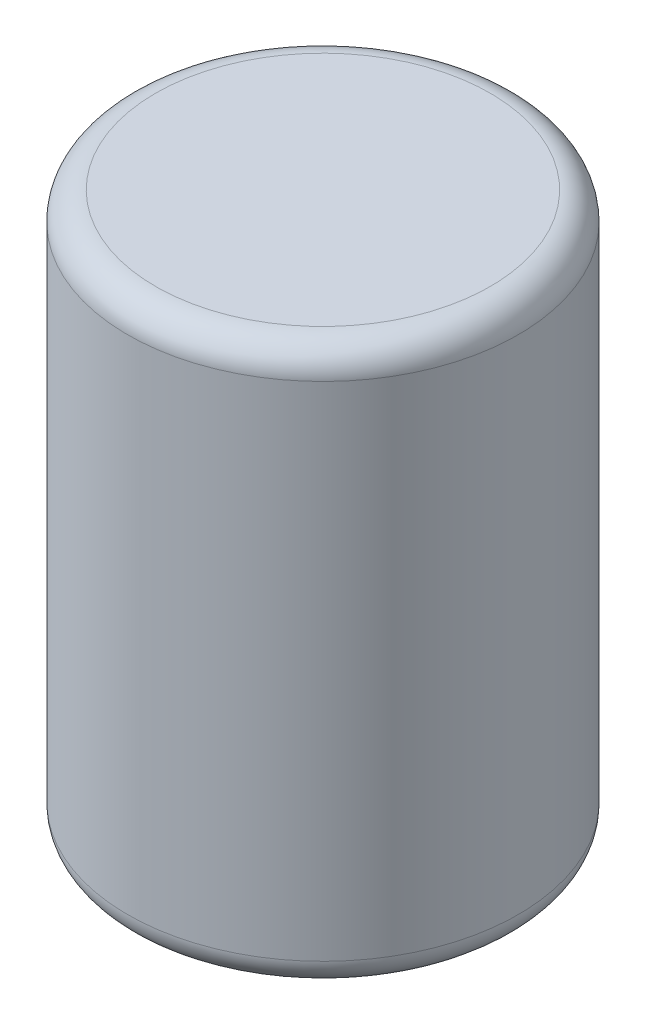
SolidWorks part; units mm, degrees
ref_plane "Front Plane" through (0, 0, 0) normal (0, 0, 1) x (1, 0, 0)
ref_plane "Top Plane" through (0, 0, 0) normal (0, 1, 0) x (1, 0, 0)
ref_plane "Right Plane" through (0, 0, 0) normal (1, 0, 0) x (0, 0, -1)
sketch "Sketch1" plane through (0, 0, 0) normal (0, 0, 1) x (1, 0, 0)
  line L0 (-0.7856, -6.2566) -> (-2.7856, -6.2566)
  line L1 (-3.7856, -5.2566) -> (-3.7856, 12.7434)
  line L2 (-2.7856, 13.7434) -> (3.2144, 13.7434)
  line L3 (3.2144, 13.7434) -> (3.2144, 3.7434)
  line L4 (3.2144, 3.7434) -> (-0.7856, 3.7434)
  line L5 (-0.7856, 3.7434) -> (-0.7856, -6.2566)
  arc A0 (-2.7856, -6.2566) -> (-3.7856, -5.2566) centre (-2.7856, -5.2566) cw
  arc A1 (-3.7856, 12.7434) -> (-2.7856, 13.7434) centre (-2.7856, 12.7434) cw
  point P8 (-3.7856, -6.2566)
  point P11 (-3.7856, 13.7434)
  dimension "D4" = 1
  dimension "D1" = 20
  dimension "D2" = 3
  dimension "D3" = 4
revolve "Revolve1" add sketch "Sketch1" angle 360 about L3
thread "Thread1" pitch 1 method extrude profile "Thread Profile1" start angle 0, offset 1, length 0, pitch 1, diameter 8
ref_plane "Plane1" through (7.2144, -7.2566, 0) normal (0, 0, 1) x (1, 0, 0)
sketch "Thread Profile1" plane through (7.2144, -7.2566, 0) normal (0, 0, 1) x (1, 0, 0)
  line L0 (0, 0) -> (0, 1) construction
  line L11 (0, 0) -> (0, 0.875)
  line L12 (0, 0.875) -> (-0.5413, 0.5625)
  line L13 (-0.5413, 0.5625) -> (-0.5413, 0.3125)
  line L15 (-0.5413, 0.3125) -> (0, 0)
  line L17 (-0.5413, 0.4375) -> (0, 0.4375) construction
  point P2 (0, 0)
  dimension "Pitch" = 1
  dimension "Profile_Angle" = 60
  dimension "Profile_Land" = 0.25
  dimension "Profile_Height" = 0.5413
ref_plane "Plane2" through (0, -6.2566, 0) normal (0, 1, 0) x (1, 0, 0)
other "SurfaceCut1"
